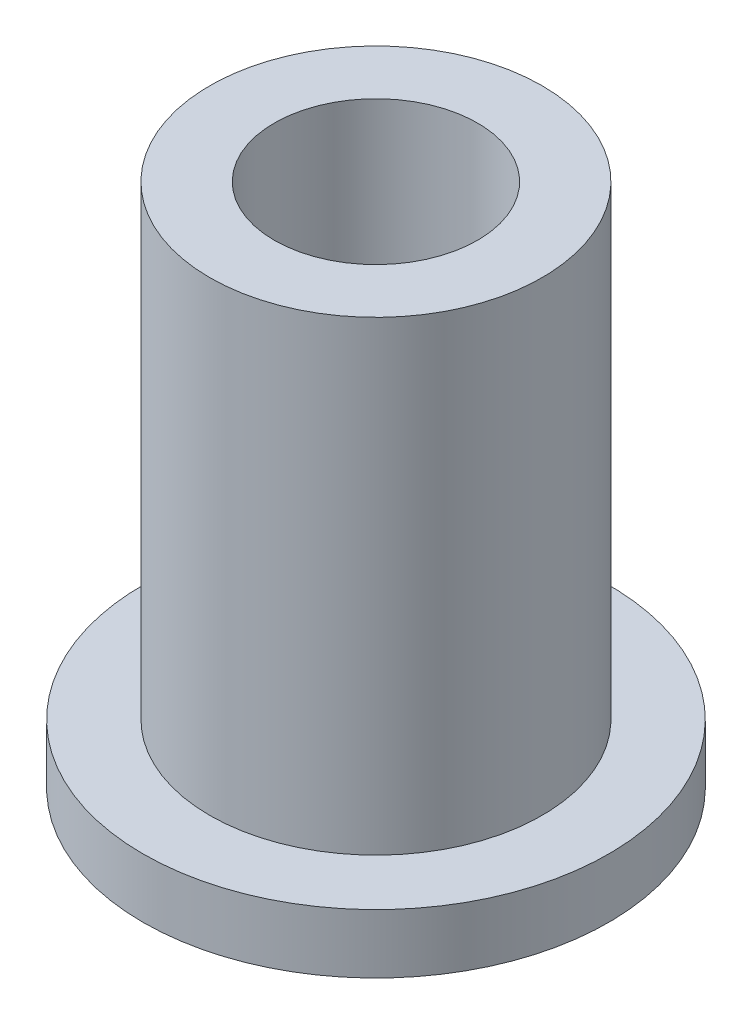
SolidWorks part; units mm, degrees
material "Commercial Bronze, UNS C22000 (90-10 Bronze)"
ref_plane "Front Plane" through (0, 0, 0) normal (0, 0, 1) x (1, 0, 0)
ref_plane "Top Plane" through (0, 0, 0) normal (0, 1, 0) x (1, 0, 0)
ref_plane "Right Plane" through (0, 0, 0) normal (1, 0, 0) x (0, 0, -1)
ref_plane "Plane1" through (0, 0, 0) normal (0, 0, -1) x (-1, 0, 0)
sketch "Sketch1" plane through (0, 0, 0) normal (0, 0, -1) x (-1, 0, 0)
  line L0 (-5.5, 0) -> (-2.6, 0)
  line L1 (-2.6, 0) -> (-2.4, 0.2)
  line L2 (-2.4, 0.2) -> (-2.4, 12.4)
  line L3 (-2.4, 12.4) -> (-3.925, 12.4)
  line L4 (-3.925, 12.4) -> (-3.925, 1.4)
  line L5 (-3.925, 1.4) -> (-5.5, 1.4)
  line L6 (-5.5, 1.4) -> (-5.5, 0)
  line L7 (0, 0) -> (0, 12.4) construction
revolve "Revolve1" add sketch "Sketch1" angle 360 about L7 reverse direction yes
